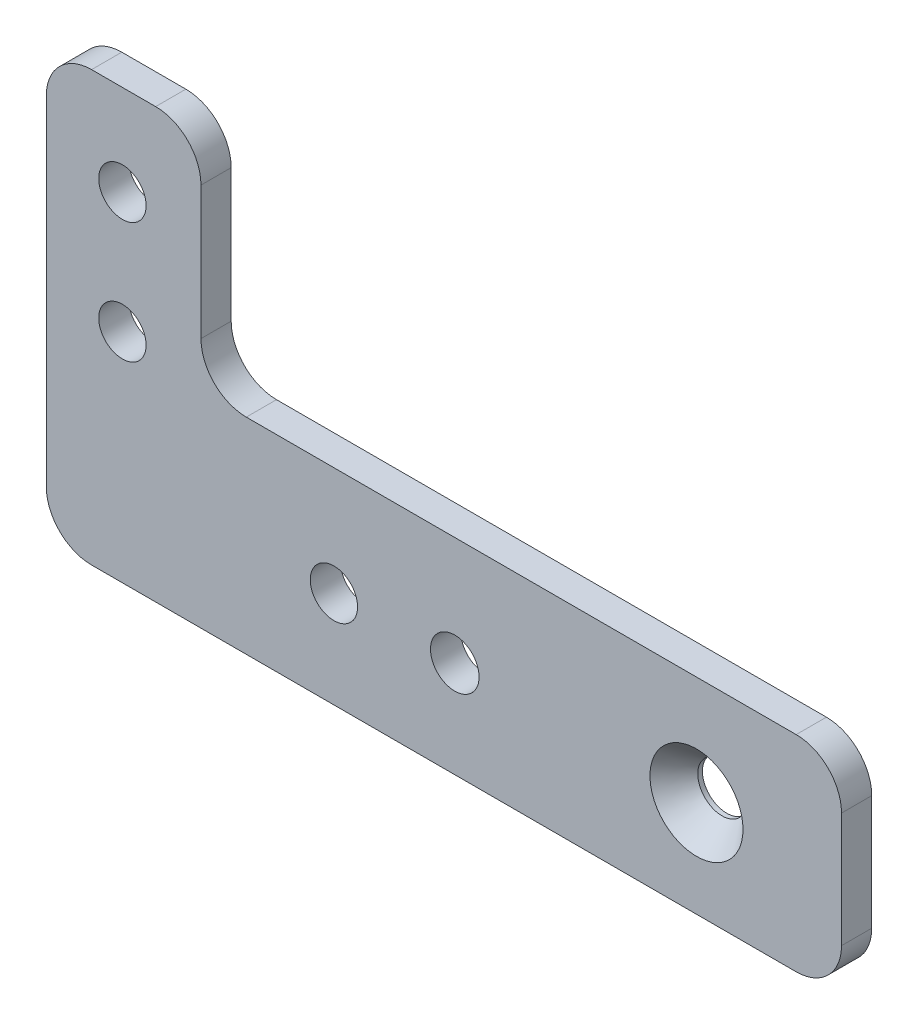
SolidWorks part; units mm, degrees
material "6061-T6 (SS)"
ref_plane "Front Plane" through (0, 0, 0) normal (0, 0, 1) x (1, 0, 0)
ref_plane "Top Plane" through (0, 0, 0) normal (0, 1, 0) x (1, 0, 0)
ref_plane "Right Plane" through (0, 0, 0) normal (1, 0, 0) x (0, 0, -1)
sketch "Sketch1" plane through (0, 0, 0) normal (0, 0, 1) x (1, 0, 0)
  line L0 (-21.59, 23.8125) -> (-37.846, 23.8125) construction
  line L1 (-45.72, -23.8125) -> (45.72, -23.8125)
  line L2 (-45.72, -23.8125) -> (-45.72, 23.8125)
  line L3 (-45.72, 23.8125) -> (45.72, 23.8125)
  line L4 (45.72, -23.8125) -> (45.72, 23.8125)
  line L5 (-45.72, -23.8125) -> (45.72, 23.8125) construction
  line L6 (-45.72, 23.8125) -> (45.72, -23.8125) construction
  line L7 (45.72, 23.8125) -> (-21.59, 23.8125)
  line L8 (45.72, 23.8125) -> (45.72, 0.3175)
  line L9 (45.72, 0.3175) -> (-21.59, 0.3175)
  line L10 (-21.59, 23.8125) -> (-21.59, 0.3175)
  line L11 (-45.72, -23.8125) -> (-37.846, -23.8125)
  line L12 (-45.72, -23.8125) -> (-45.72, 23.8125)
  line L13 (-45.72, 23.8125) -> (-37.846, 23.8125)
  line L14 (-37.846, -23.8125) -> (-37.846, 23.8125)
  line L15 (-37.846, -23.8125) -> (45.72, -23.8125)
  line L16 (-37.846, -23.8125) -> (-37.846, -21.2725)
  line L17 (-37.846, -21.2725) -> (45.72, -21.2725)
  line L18 (45.72, -23.8125) -> (45.72, -21.2725)
  line L19 (-21.59, 23.8125) -> (-37.846, 23.8125) construction
  line L20 (-29.845, 23.8125) -> (-29.845, -21.2725) construction
  circle A0 centre (-29.845, -11.1125) radius 2.4892
  circle A1 centre (-29.845, 1.5875) radius 2.4892
  circle A2 centre (-29.845, 14.2875) radius 2.4892
  circle A4 centre (-7.62, -11.1125) radius 2.4892
  circle A5 centre (5.08, -11.1125) radius 2.5527
  circle A7 centre (30.48, -11.1125) radius 2.5527
  point P0 (0, 0)
  point P31 (0, 0)
  dimension "D7" = 22.225
  dimension "D18" = 5.1054
  dimension "D19" = 4.9784
  dimension "D13" = 25.4
  dimension "D8" = 50.8
  dimension "D1" = 91.44
  dimension "D2" = 9.525
  dimension "D3" = 24.13
  dimension "D4" = 24.13
  dimension "D5" = 7.874
  dimension "D6" = 47.625
  dimension "D9" = 12.7
  dimension "D10" = 12.7
  dimension "D11" = 12.7
  dimension "D12" = 15.875
  dimension "D16" = 2.54
extrude "Boss-Extrude1" add sketch "Sketch1" along normal blind 3.175 contours L14 L17 L4 L9 L10 L3 A5 A4 A2 A1 A0 | A0 region at (-1.4918, -6.6351, 0) region at (-29.845, -11.1125, 0)
fillet "Fillet1" radius 4.7625 6 edges at (-37.846, 23.8125, 1.5875) (-21.59, 23.8125, 1.5875) (-21.59, 0.3175, 1.5875) (45.72, 0.3175, 1.5875) (45.72, -21.2725, 1.5875) (-37.846, -21.2725, 1.5875)
hole_wizard "CSK for #10 Flat Head Machine Screw1" positions "Sketch3" profile "Sketch4" countersink size "#10" standard "ANSI Inch"
sketch "Sketch3" plane through (0, 0, 3.175) normal (0, 0, 1) x (1, 0, 0)
  point P0 (30.48, -11.1125)
sketch "Sketch4" plane through (30.48, -11.1125, 3.175) normal (1, 0, 0) x (0, -1, 0)
  line L0 (0, 0) -> (0, 20.5838)
  line L1 (0, 20.5838) -> (2.5527, 19.05)
  line L2 (2.5527, 19.05) -> (2.5527, 2.6882)
  line L3 (2.5527, 2.6882) -> (4.8895, 0)
  line L5 (4.8895, 0) -> (0, 0)
  line L6 (-2.5527, 2.6882) -> (-4.8895, 0) construction
  line L10 (0, 20.5838) -> (-2.5527, 19.05) construction
  line L11 (0, -6.35) -> (0, 107.95) construction
  dimension "Hole Dia." = 5.1054
  dimension "Hole Depth" = 19.05
  dimension "Near C'Sink Dia." = 9.779
  dimension "Near C'Sink Angle" = 82
  dimension "Drill Angle" = 118
